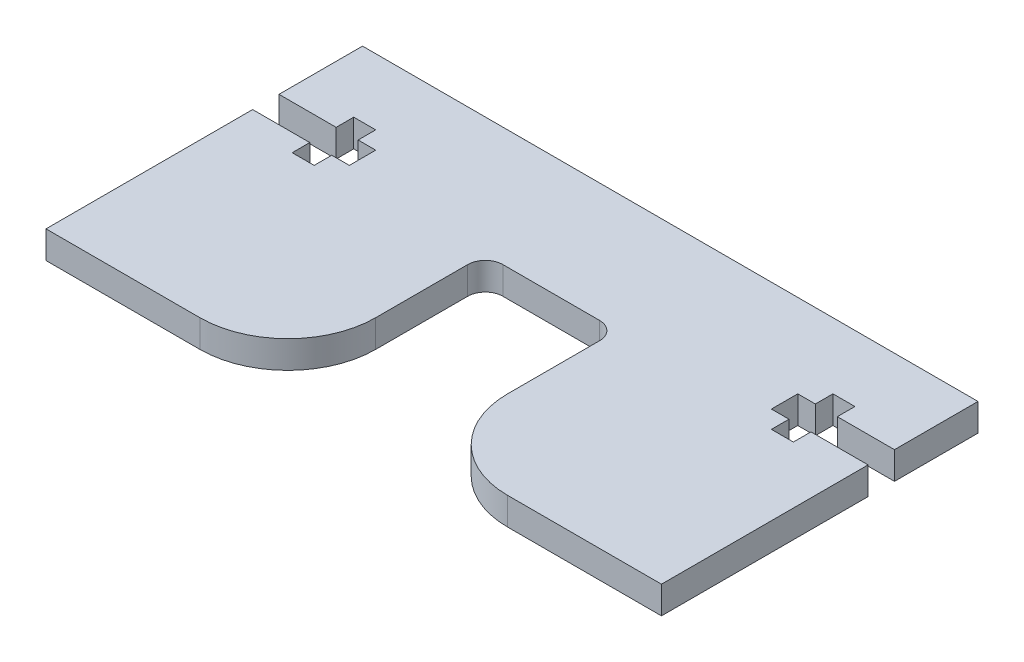
SolidWorks part; units mm, degrees
ref_plane "Front Plane" through (0, 0, 0) normal (0, 0, 1) x (1, 0, 0)
ref_plane "Top Plane" through (0, 0, 0) normal (0, 1, 0) x (1, 0, 0)
ref_plane "Right Plane" through (0, 0, 0) normal (1, 0, 0) x (0, 0, -1)
sketch "Sketch1" plane through (0, 0, 0) normal (0, 1, 0) x (1, 0, 0)
  line L0 (0, 25) -> (35, 25) construction
  line L1 (0, 36) -> (35, 36)
  line L2 (0, 36) -> (0, 0)
  line L3 (0, 0) -> (35, 0)
  line L4 (35, 36) -> (35, 26.5)
  line L5 (35, 26.5) -> (28.5, 26.5)
  line L6 (28.5, 26.5) -> (28.5, 28.5)
  line L7 (28.5, 28.5) -> (26, 28.5)
  line L8 (26, 28.5) -> (26, 26.5)
  line L9 (26, 26.5) -> (24, 26.5)
  line L10 (24, 26.5) -> (24, 23.5)
  line L11 (24, 23.5) -> (26, 23.5)
  line L12 (26, 23.5) -> (26, 21.5)
  line L13 (26, 21.5) -> (28.5, 21.5)
  line L14 (28.5, 21.5) -> (28.5, 23.5)
  line L15 (28.5, 23.5) -> (35, 23.5)
  line L16 (35, 23.5) -> (35, 0)
  point P17 (24, 25)
  dimension "D1" = 35
  dimension "D2" = 2.5
  dimension "D3" = 9
  dimension "D4" = 2
  dimension "D5" = 3
  dimension "D6" = 7.5
  dimension "D7" = 7
  dimension "D8" = 25
extrude "Boss-Extrude1" add sketch "Sketch1" along normal mid plane 3.125
mirror "Mirror1" about plane through (0, 0, 0) normal (1, 0, 0) of "Boss-Extrude1"
sketch "Sketch2" plane through (0, -1.5625, 0) normal (0, -1, 0) x (1, 0, 0)
  line L0 (-35, 0) -> (35, 0) construction
  line L1 (-7.5, 0) -> (7.5, 0)
  line L2 (-7.5, 0) -> (-7.5, -22.4625)
  line L3 (-7.5, -22.4625) -> (7.5, -22.4625)
  line L4 (7.5, 0) -> (7.5, -22.4625)
  line L5 (-7.5, 0) -> (7.5, -22.4625) construction
  line L6 (-7.5, -22.4625) -> (7.5, 0) construction
  line L7 (0, -11.2313) -> (0, 0) construction
  line L8 (-35, -9.9625) -> (35, -9.9625) construction
  point P4 (0, -11.2313)
  dimension "D1" = 15
  dimension "D2" = 12.5
extrude "Cut-Extrude1" cut sketch "Sketch2" against normal through all
fillet "Fillet1" radius 10 2 edges at (-7.5, 0, 0) (7.5, 0, 0)
fillet "Fillet2" radius 2 2 edges at (7.5, 0, -22.4625) (-7.5, 0, -22.4625)
